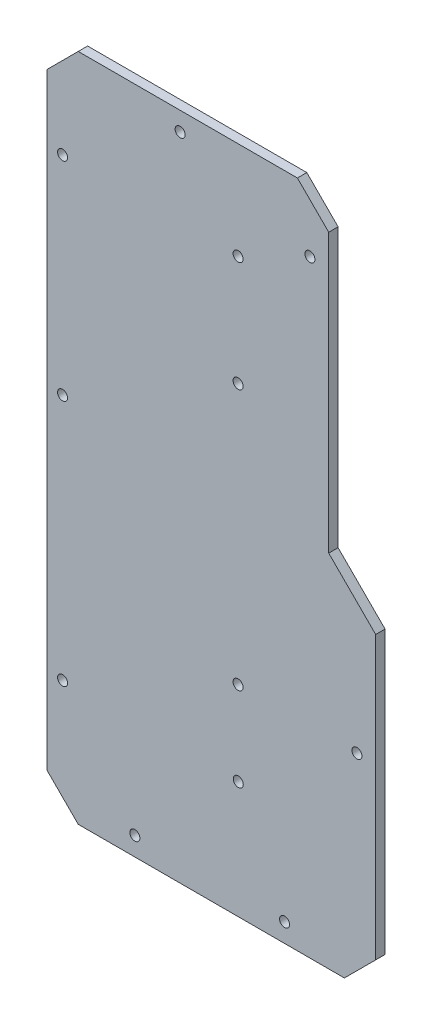
SolidWorks part; units mm, degrees
ref_plane "Front Plane" through (0, 0, 0) normal (0, 0, 1) x (1, 0, 0)
ref_plane "Top Plane" through (0, 0, 0) normal (0, 1, 0) x (1, 0, 0)
ref_plane "Right Plane" through (0, 0, 0) normal (1, 0, 0) x (0, 0, -1)
sketch "Sketch1" plane through (0, 0, 0) normal (0, 0, 1) x (1, 0, 0)
  line L0 (-80, -143.754) -> (-80, 4.2435) construction
  line L1 (-70, 34.0035) -> (0, 34.0035)
  line L2 (-80, 24.0035) -> (-80, -169.754)
  line L3 (-70, -179.754) -> (0, -179.754)
  line L6 (-14, -149.754) -> (-80, -149.754) construction
  line L8 (10, -64.754) -> (10, 24.0035)
  line L9 (-80, 24.0035) -> (-70, 34.0035)
  line L10 (10, 24.0035) -> (0, 34.0035)
  line L11 (-80, -169.754) -> (-70, -179.754)
  line L13 (10, -64.754) -> (25, -79.754)
  line L14 (25, -79.754) -> (25, -169.754)
  line L15 (15, -179.754) -> (0, -179.754)
  line L16 (25, -169.754) -> (15, -179.754)
  line L17 (-80, 10.2435) -> (-14, 10.2435) construction
  circle A0 centre (-75, 2.8935) radius 1.6
  circle A1 centre (-18.9466, 2.8935) radius 1.6
  circle A2 centre (-75, -142.404) radius 1.6
  circle A3 centre (-18.8932, -142.404) radius 1.6
  circle A4 centre (-75, -63.5502) radius 1.6 construction
  circle A5 centre (-18.9466, -115.5824) radius 1.6 construction
  circle A6 centre (4, 14.2435) radius 1.6
  circle A7 centre (-37.4508, 28.0035) radius 1.6
  circle A8 centre (-18.9466, -32.301) radius 1.6 construction
  circle A9 centre (-75, -63.5502) radius 1.6
  circle A10 centre (-18.9466, -115.5824) radius 1.6
  circle A11 centre (-18.9466, -32.301) radius 1.6
  circle A12 centre (19, -115.5824) radius 1.6
  circle A13 centre (-51.915, -173.754) radius 1.6
  circle A14 centre (-4.1152, -173.754) radius 1.6
  point P0 (-80, 34.0035)
  point P2 (-80, -179.754)
  point P12 (10, 34.0035)
  point P32 (25, -179.754)
  dimension "D2" = 3.2
  dimension "D14" = 3.2
  dimension "D16" = 6
  dimension "D17" = 6
  dimension "D1" = 30
  dimension "D3" = 90
  dimension "D4" = 45
  dimension "D6" = 23.76
  dimension "D11" = 6
  dimension "D7" = 100
  dimension "D10" = 15
  dimension "D13" = 6
  dimension "D15" = 6
extrude "Extrude1" add sketch "Sketch1" along normal blind 3
